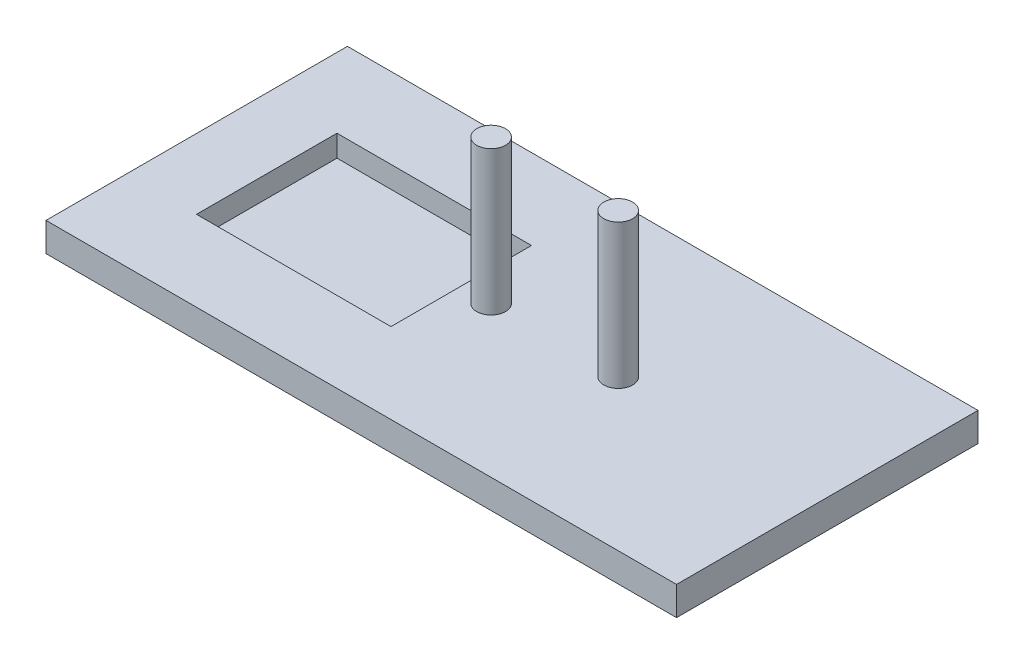
SolidWorks part; units mm, degrees
ref_plane "Front Plane" through (0, 0, 0) normal (0, 0, 1) x (1, 0, 0)
ref_plane "Top Plane" through (0, 0, 0) normal (0, 1, 0) x (1, 0, 0)
ref_plane "Right Plane" through (0, 0, 0) normal (1, 0, 0) x (0, 0, -1)
sketch "Sketch1" plane through (0, 0, 0) normal (0, 1, 0) x (1, 0, 0)
  line L0 (-43.77, 0) -> (43.77, 0) construction
  line L1 (-43.77, -20.9265) -> (43.77, -20.9265)
  line L2 (-43.77, -20.9265) -> (-43.77, 20.9265)
  line L3 (-43.77, 20.9265) -> (43.77, 20.9265)
  line L4 (43.77, -20.9265) -> (43.77, 20.9265)
  line L5 (-43.77, -20.9265) -> (43.77, 20.9265) construction
  line L6 (-43.77, 20.9265) -> (43.77, -20.9265) construction
  line L8 (-34.0502, -9.75) -> (-7.0502, -9.75)
  line L9 (-34.0502, -9.75) -> (-34.0502, 9.75)
  line L10 (-34.0502, 9.75) -> (-7.0502, 9.75)
  line L11 (-7.0502, -9.75) -> (-7.0502, 9.75)
  line L12 (-34.0502, -9.75) -> (-7.0502, 9.75) construction
  line L13 (-34.0502, 9.75) -> (-7.0502, -9.75) construction
  circle A0 centre (-20.5502, 0) radius 6
  circle A1 centre (-2.9004, 0) radius 11.6498
  circle A2 centre (-2.9004, 0) radius 6
  circle A3 centre (14.7494, 0) radius 11.6498
  circle A4 centre (14.7494, 0) radius 6
  circle A5 centre (14.7494, 0) radius 2
  circle A7 centre (-2.9004, 0) radius 2
  point P0 (0, 0)
  dimension "D1" = 12
  dimension "D2" = 23.2996
  dimension "D5" = 4
  dimension "D3" = 19.5
  dimension "D4" = 27
sketch "Sketch2" plane through (0, 0, 0) normal (0, 1, 0) x (1, 0, 0)
  line L2 (-43.77, -20.9265) -> (43.77, -20.9265)
  line L3 (-43.77, -20.9265) -> (-43.77, 20.9265)
  line L4 (-43.77, 20.9265) -> (43.77, 20.9265)
  line L5 (43.77, -20.9265) -> (43.77, 20.9265)
  line L6 (-43.77, -20.9265) -> (43.77, 20.9265) construction
  line L7 (-43.77, 20.9265) -> (43.77, -20.9265) construction
  line L8 (-7.0502, -9.75) -> (-34.0502, -9.75)
  line L9 (-7.0502, -9.75) -> (-7.0502, 9.75)
  line L10 (-7.0502, 9.75) -> (-34.0502, 9.75)
  line L11 (-34.0502, -9.75) -> (-34.0502, 9.75)
  line L12 (-7.0502, -9.75) -> (-34.0502, 9.75) construction
  line L13 (-7.0502, 9.75) -> (-34.0502, -9.75) construction
  point P0 (-20.5502, 0)
  point P2 (0, 0)
extrude "Boss-Extrude1" add sketch "Sketch2" against normal blind 4 contours L11 L8 L9 L10 | L2 L5 L4 L3 L8 L11 L10 L9 region at (3.4487, 0, 0) region at (-20.5502, 0, 0)
extrude "Cut-Extrude1" cut sketch "Sketch2<4>" against normal blind 3 contours L11 L8 L9 L10 region at (-20.5502, 0, 0)
sketch "Sketch2<4>" plane through (0, 0, 0) normal (0, 1, 0) x (1, 0, 0) same geometry as "Sketch2"
extrude "Boss-Extrude2" add sketch "Sketch1" along normal blind 20 contours A5 | A7 region at (14.7494, 0, 0)
equation "\"D1@Sketch1\"=2*6.00mm"
equation "\"D2@Sketch1\"=2*11.6498mm"
